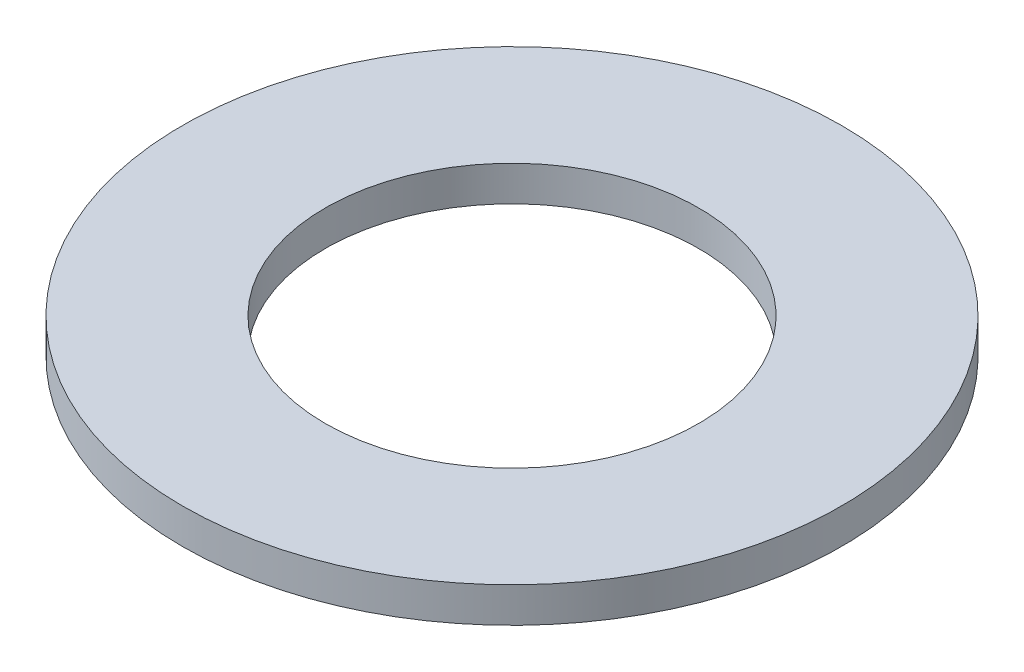
SolidWorks part; units mm, degrees
ref_plane "Front Plane" through (0, 0, 0) normal (0, 0, 1) x (1, 0, 0)
ref_plane "Top Plane" through (0, 0, 0) normal (0, 1, 0) x (1, 0, 0)
ref_plane "Right Plane" through (0, 0, 0) normal (1, 0, 0) x (0, 0, -1)
sketch "Sketch1" plane through (0, 0, 0) normal (0, 1, 0) x (1, 0, 0)
  circle A0 centre (0, 0) radius 75
  dimension "FLANGE_OD" = 150
extrude "Boss-Extrude1" add sketch "Sketch1" along normal blind 8
sketch "Sketch2" plane through (0, 0, 0) normal (0, 1, 0) x (1, 0, 0)
  circle A0 centre (0, 0) radius 42.5
  dimension "BORE_D" = 85
extrude "Cut-Extrude1" cut sketch "Sketch2" along normal through all
sketch "Sketch3" plane through (0, 8, 0) normal (0, 1, 0) x (1, 0, 0)
  circle A0 centre (0, 0) radius 35.5801 construction
  circle A1 centre (-35.5801, 0) radius 2.3378
  dimension "BOLT_D" = 4.6757
  dimension "BOLT_PCD" = 71.1602
extrude "Cut-Extrude2" cut sketch "Sketch3" against normal blind 6.6914 rebuild error yes
pattern_circular "CirPattern1" count 8 over 360 rebuild error yes
